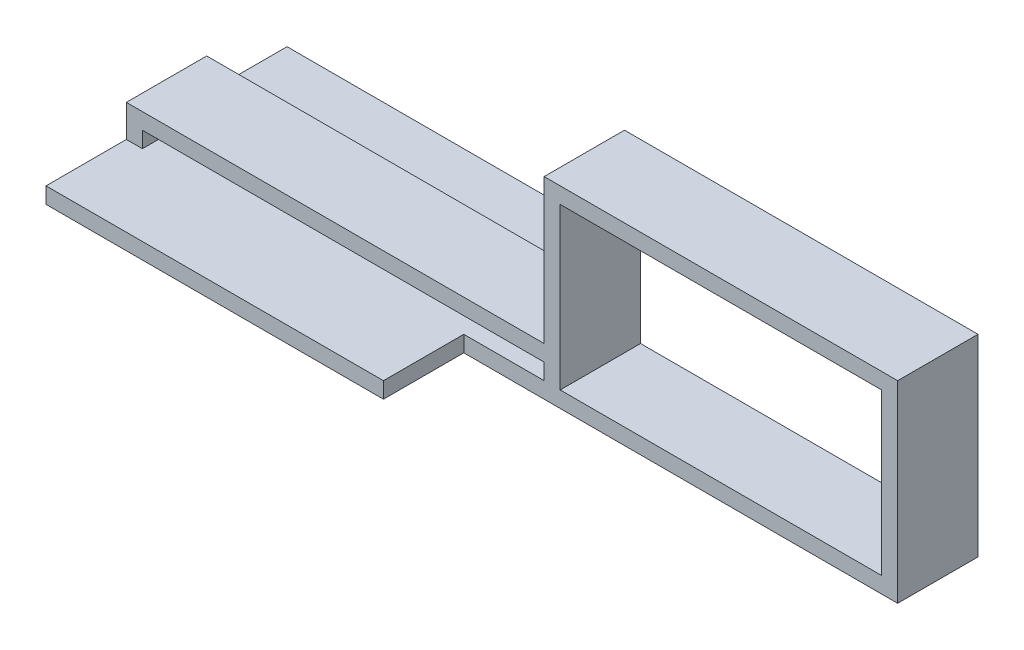
SolidWorks part; units mm, degrees
ref_plane "前视基准面" through (0, 0, 0) normal (0, 0, 1) x (1, 0, 0)
ref_plane "上视基准面" through (0, 0, 0) normal (0, 1, 0) x (1, 0, 0)
ref_plane "右视基准面" through (0, 0, 0) normal (1, 0, 0) x (0, 0, -1)
sketch "草图1" plane through (0, 0, 0) normal (0, 0, 1) x (1, 0, 0)
  line L1 (-20.1706, -2.2873) -> (19.8294, -2.2873)
  line L2 (-20.1706, -2.2873) -> (-20.1706, -22.2873)
  line L3 (-20.1706, -22.2873) -> (19.8294, -22.2873)
  line L4 (19.8294, -2.2873) -> (19.8294, -22.2873)
  line L8 (-22.1706, -24.2873) -> (21.8294, -24.2873)
  line L10 (-22.1706, -22.2873) -> (-22.1706, -20.2873)
  line L11 (-22.1706, -0.2873) -> (21.8294, -0.2873)
  line L12 (21.8294, -0.2873) -> (21.8294, -24.2873)
  line L16 (-22.1706, -24.2873) -> (-74.1706, -24.2873)
  line L17 (-74.1706, -24.2873) -> (-74.1706, -18.2873)
  line L18 (-74.1706, -18.2873) -> (-22.1706, -18.2873)
  line L19 (-74.1706, -24.2873) -> (-74.1706, -22.2873)
  line L21 (-72.1706, -22.2873) -> (-72.1706, -20.2873)
  line L22 (-72.1706, -20.2873) -> (-22.1706, -20.2873)
  line L23 (-22.1706, -20.2873) -> (-22.1706, -22.2873)
  line L24 (-22.1706, -22.2873) -> (-72.1706, -22.2873)
  line L25 (-22.1706, -18.2873) -> (-22.1706, -0.2873)
  line L29 (-74.1706, -24.2873) -> (-22.1706, -24.2873)
  line L30 (-74.1706, -24.2873) -> (-74.1706, -22.2873)
  line L31 (-72.1706, -22.2873) -> (-22.1706, -22.2873)
extrude "凸台-拉伸1" add sketch "草图1" along normal blind 5 and the other way blind 5 contours L10 L8 L12 L11 L25 L18 L17 L21 L22 L1 L4 L3 L2 region at (-22.1279, -16.3642, 0)
sketch "草图2" plane through (0, 0, 5) normal (0, 0, 1) x (1, 0, 0)
  line L0 (-22.1706, -24.2873) -> (-32.1706, -24.2873)
  line L1 (21.8294, -24.2873) -> (-74.1706, -24.2873) construction
  line L2 (-32.1706, -24.2873) -> (-32.1706, -22.2873)
  line L3 (-22.1706, -22.2873) -> (-72.1706, -22.2873) construction
  line L4 (-32.1706, -22.2873) -> (-74.1706, -22.2873)
  line L5 (-74.1706, -22.2873) -> (-74.1706, -24.2873)
  line L6 (-74.1706, -24.2873) -> (-32.1706, -24.2873)
  line M3 (-74.1706, -18.2873) -> (-74.1706, -24.2873)
  line M4 (-74.1706, -24.2873) -> (21.8294, -24.2873)
  line M12 (-22.1706, -22.2873) -> (-72.1706, -22.2873)
extrude "凸台-拉伸2" add sketch "草图2" along normal blind 10 and the other way blind 20 contours L4 L2 M12 M3 M4 region at (-53.1706, -23.2873, 5)
